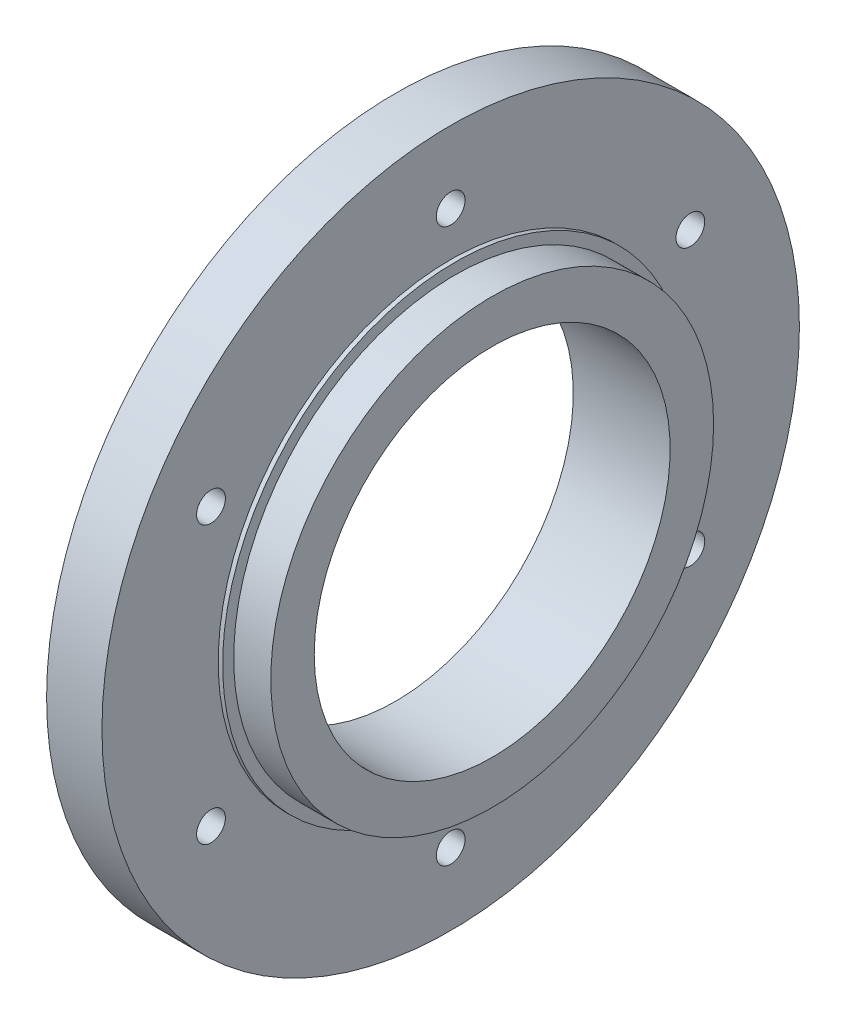
SolidWorks part; units mm, degrees
ref_plane "Ebene vorne" through (0, 0, 0) normal (0, 0, 1) x (1, 0, 0)
ref_plane "Ebene oben" through (0, 0, 0) normal (0, 1, 0) x (1, 0, 0)
ref_plane "Ebene rechts" through (0, 0, 0) normal (1, 0, 0) x (0, 0, -1)
sketch "Skizze1" plane through (0, 0, 0) normal (0, 0, 1) x (1, 0, 0)
  line L0 (0, 0) -> (-40471.317, 0) construction
  line L1 (0, 0) -> (0, 31.5)
  line L2 (0, 31.5) -> (5, 31.5)
  line L3 (5, 31.5) -> (5, 21)
  line L4 (5, 21) -> (5.4, 21)
  line L6 (8.75, 0) -> (0, 0)
  line L7 (8.75, 0) -> (8.75, 20)
  line L8 (8.75, 20) -> (5.4, 20)
  line L9 (5.4, 21) -> (5.4, 20)
  dimension "D1" = 42
  dimension "D2" = 0.4
  dimension "D3" = 3.35
  dimension "D4" = 63
  dimension "D5" = 40
  dimension "D6" = 8.75
revolve "Rotation1" add sketch "Skizze1" angle 360 about L0
sketch "Skizze2" plane through (0, 0, 0) normal (-1, 0, 0) x (0, 0, 1)
  circle A0 centre (0, 0) radius 16.075
  dimension "D1" = 32.15
extrude "Schnitt-Linear austragen1" cut sketch "Skizze2" against normal through all
sketch "Skizze3" plane through (5, 0, 0) normal (1, 0, 0) x (0, 0, -1)
  line L0 (0, 0) -> (0, -50000) construction
  line L2 (1.7321, 22) -> (3.4641, 25)
  line L3 (3.4641, 25) -> (1.7321, 28)
  line L4 (1.7321, 28) -> (-1.7321, 28)
  line L5 (-1.7321, 28) -> (-3.4641, 25)
  line L6 (-3.4641, 25) -> (-1.7321, 22)
  line L7 (-1.7321, 22) -> (1.7321, 22)
  circle A0 centre (0, 25) radius 3 construction
  circle A1 centre (0, 0) radius 25 construction
  dimension "D2" = 50
  dimension "D1" = 6
hole_wizard "Ø2.6 (2.6) Durchmesser Bohrung1" positions "Skizze4" profile "Skizze5" hole size "Ø2.6" standard "ISO" end condition through all
sketch "Skizze4" plane through (5, 0, 0) normal (1, 0, 0) x (0, 0, -1)
  line L0 (0, 0) -> (0, -50000) construction
  circle A0 centre (0, 0) radius 25 construction
  point P9 (0, 25)
  dimension "D1" = 50
sketch "Skizze5" plane through (5, 25, 0) normal (0, 1, 0) x (0, 0, -1)
  line L0 (0, 0) -> (0, 5)
  line L1 (0, 5) -> (1.3, 5)
  line L2 (1.3, 5) -> (1.3, 0)
  line L5 (1.3, 0) -> (0, 0)
  line L11 (0, -6.35) -> (0, 107.95) construction
  dimension "Bohrerdurchmesser" = 2.6
  dimension "Bohrungstiefe" = 5
pattern_circular "Kreismuster2" count 6 over 360 about axis through (8.75, 0, 0) along (-1, 0, 0) of "Ø2.6 (2.6) Durchmesser Bohrung1"
